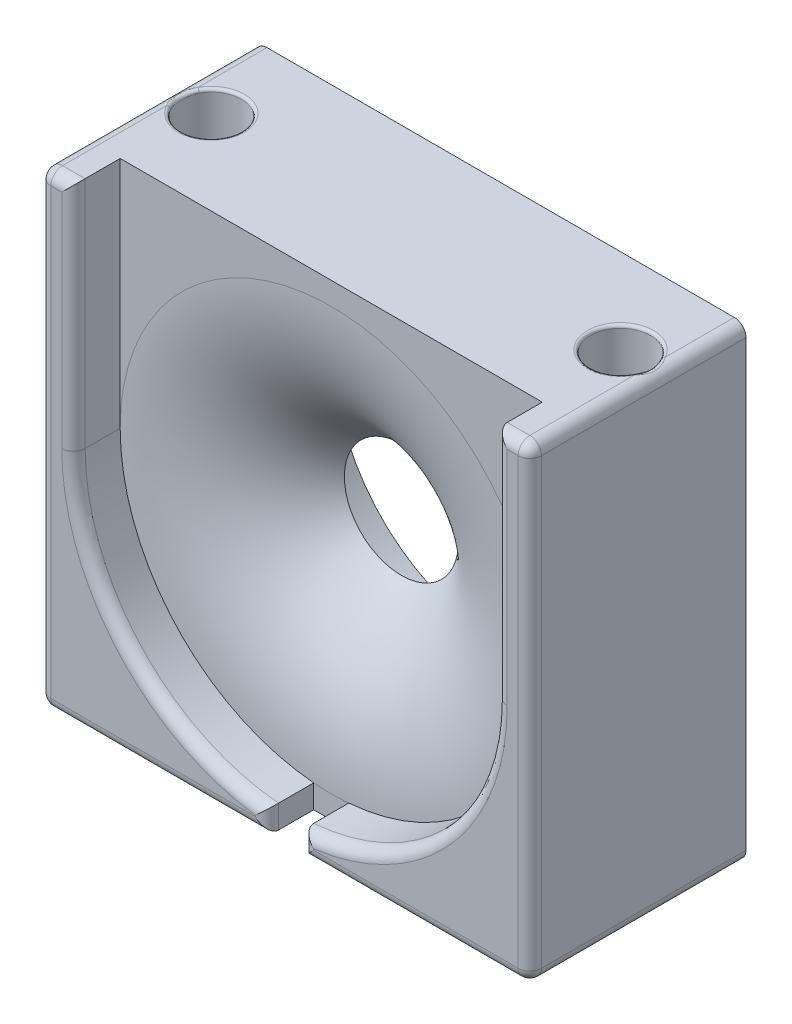
SolidWorks part; units mm, degrees
ref_plane "Front Plane" through (0, 0, 0) normal (1, 0, 0) x (0, 1, 0)
ref_plane "Top Plane" through (0, 0, 0) normal (0, 0, 1) x (0, 1, 0)
ref_plane "Right Plane" through (0, 0, 0) normal (0, 1, 0) x (-1, 0, 0)
sketch "Sketch1" plane through (0, 0, 0) normal (0, 0, 1) x (0, 1, 0)
  line L1 (-40, -42) -> (40, -42)
  line L2 (-40, -42) -> (-40, 42)
  line L3 (-40, 42) -> (40, 42)
  line L4 (40, -42) -> (40, 42)
  line L5 (-40, -42) -> (40, 42) construction
  line L6 (-40, 42) -> (40, -42) construction
  circle A0 centre (0, 0) radius 9.75
  point P0 (0, 0)
  dimension "D3" = 19.5
  dimension "D1" = 84
  dimension "D2" = 80
extrude "29 mm extrude" add sketch "Sketch1" along normal blind 29
sketch "Sketch2" plane through (0, 0, 0) normal (0, 0, -1) x (1, 0, 0)
  circle A0 centre (0, 0) radius 28.5
  dimension "D1" = 57
extrude "17 mm cut" cut sketch "Sketch2" against normal blind 17
fillet "25R funnel slope" radius 35 1 edges at (9.75, 0, 29)
sketch "Sketch3" plane through (0, 40, 0) normal (0, 1, 0) x (-1, 0, 0)
  line L0 (-42, 14.5) -> (42, 14.5) construction
  line L1 (-42, 29) -> (-42, 0) construction
  line L2 (42, 29) -> (42, 0) construction
  line L3 (0, 29) -> (0, 0) construction
  line L4 (-42, 29) -> (42, 29) construction
  line L5 (-42, 14.5) -> (-40.175, 14.5)
  circle A0 centre (-35.025, 14.5) radius 5.15
  circle A1 centre (35.025, 14.5) radius 5.15
  dimension "D1" = 10.3
extrude "36 mm cut screw head" cut sketch "Sketch3" against normal blind 36 contours A0 | A1 region at (35.025, 40, 14.5) region at (-35.025, 40, 14.5)
sketch "Sketch5" plane through (0, 40, 0) normal (0, 1, 0) x (-1, 0, 0)
  circle A0 centre (-35.025, 14.5) radius 3.9
  circle A1 centre (-35.025, 14.5) radius 5.15 construction
  dimension "D1" = 7.8
extrude "7.8mm bore" cut sketch "Sketch5" against normal through all
fillet "3R pig hole" radius 5 1 edges at (-28.5, 0, 17)
fillet "2R corners" radius 2 4 edges at (-42, 40, 14.5) (-42, -40, 14.5) (42, -40, 14.5) (42, 40, 14.5)
fillet "0.5R bolts" radius 0.5 4 edges at (-40.1603, 39.9936, 14.8885) (40.1603, 39.9936, 14.1115) (-29.875, 40, 14.5) (29.875, 40, 14.5)
mirror "Mirror1" about plane through (0, 0, 0) normal (1, 0, 0) of "7.8mm bore"
sketch "Sketch6" plane through (0, 0, 29) normal (0, 0, 1) x (1, 0, 0)
  line L0 (-42, 38) -> (-42, -38) construction
  line L1 (-42, 0) -> (42, 0)
  line L2 (-42, 38) -> (-42, -38)
  line L3 (-40, -40) -> (40, -40)
  line L4 (42, 38) -> (42, -38)
  line L5 (-42, 0) -> (42, -40) construction
  line L6 (-42, -40) -> (42, 0) construction
  line L7 (42, -38) -> (42, 38) construction
  line L8 (-40, -40) -> (40, -40) construction
  line L9 (-39, -3) -> (-39, -37)
  line L10 (-39, -37) -> (39, -37)
  line L11 (39, -3) -> (39, -37)
  line L12 (-39, -3) -> (39, -3)
  line L13 (-42, -3) -> (42, -3)
  line L14 (-42, 0) -> (-42, -40) construction
  line L15 (-42, -40) -> (42, -40) construction
  line L16 (42, 0) -> (42, -40) construction
  line L17 (0, -37) -> (0, -40) construction
  line L18 (-3, 31.0296) -> (3, 37) construction
  line L19 (-3, -40) -> (3, -40)
  line L20 (-3, -40) -> (-3, -37)
  line L21 (-3, -37) -> (3, -37)
  line L22 (3, -40) -> (3, -37)
  line L23 (-3, -40) -> (3, -37) construction
  line L24 (-3, -37) -> (3, -40) construction
  line L25 (-3, -37) -> (3, -37)
  line L26 (-3, -37) -> (-3, -31.0296)
  line L27 (-3, -31.0296) -> (3, -31.0296)
  line L28 (3, -37) -> (3, -31.0296)
  line L29 (-3, -37) -> (3, -31.0296) construction
  line L30 (-3, -31.0296) -> (3, -37) construction
  line L31 (-3, 37) -> (3, 31.0296) construction
  line L32 (-3, 37) -> (3, 40) construction
  line L33 (-3, 40) -> (3, 37) construction
  line L34 (0, 37) -> (0, 40) construction
  line L35 (-42, 40) -> (42, 0) construction
  line L36 (-42, 0) -> (42, 40) construction
  line L37 (3, 37) -> (3, 31.0296)
  line L38 (-3, 31.0296) -> (3, 31.0296)
  line L39 (-3, 37) -> (-3, 31.0296)
  line L40 (-3, 37) -> (3, 37)
  line L41 (3, 40) -> (3, 37)
  line L42 (-3, 37) -> (3, 37)
  line L43 (-3, 40) -> (-3, 37)
  line L44 (-3, 40) -> (3, 40)
  line L45 (-42, 3) -> (42, 3)
  line L46 (-39, 3) -> (39, 3)
  line L47 (39, 3) -> (39, 37)
  line L48 (-39, 37) -> (39, 37)
  line L49 (-39, 3) -> (-39, 37)
  line L50 (-40, 40) -> (40, 40)
  line L51 (-36.1318, 0) -> (-36.1318, 40)
  line L52 (36.1318, 0) -> (36.1318, 40)
  arc A0 (40, 40) -> (42, 38) centre (40, 38) cw
  arc A1 (-42, -38) -> (-40, -40) centre (-40, -38) ccw
  arc A2 (40, -40) -> (42, -38) centre (40, -38) ccw
  circle A3 centre (0, 0) radius 31.1743
  arc A4 (-42, 38) -> (-40, 40) centre (-40, 38) cw
  circle A5 centre (0, 0) radius 36.1318 construction
  point P4 (0, -20)
  point P19 (0, -38.5)
  point P36 (0, -34.0148)
  point P55 (0, 34.0148)
  point P56 (0, 38.5)
  point P61 (0, 20)
  circle M11 centre (0, 0) radius 36.1318
  line M12 (40, 40) -> (-40, 40)
  arc M13 (-40, 40) -> (-42, 38) centre (-40, 38) ccw
  line M14 (-42, 38) -> (-42, -38)
  arc M15 (-42, -38) -> (-40, -40) centre (-40, -38) ccw
  line M16 (-40, -40) -> (40, -40)
  arc M17 (40, -40) -> (42, -38) centre (40, -38) ccw
  line M18 (42, -38) -> (42, 38)
  arc M19 (42, 38) -> (40, 40) centre (40, 38) ccw
  dimension "D2" = 2
  dimension "D1" = 3
  dimension "D3" = 6
extrude "8 mm extrude" add sketch "Sketch6" along normal blind 8 contours L20 L10 L9 L13 L2 M16 M15 | L22 L13 L11 L10 M16 M17 M18 | L28 L10 L11 L12 M11 | L10 L26 L12 L9 M11 | L48 L51 L50 L45 L49 M13 M14 | L45 L51 L48 L49 | L52 L48 L47 L45 L4 M19 M12 | L52 L46 L47 L48 | L52 L1 L45 L46 M18 | L12 L13 L4 L1 M11 | L1 L51 L45 L2 | L13 L12 L1 M14 M11 region at (-39.0659, 1.5, 29) region at (-39.045, -1.5053, 29) region at (-40.2798, 22.6013, 29) region at (-40.5, -3.5376, 29) region at (-37.5659, 20, 29) region at (-29.7469, -26.7336, 29) region at (39.0659, 1.5, 29) region at (39.045, -1.5053, 29) region at (29.7469, -26.7336, 29) region at (37.5659, 20, 29) region at (21, -37.5376, 29) region at (40.2798, 22.6013, 29)
fillet "1R filet" radius 2 16 edges at (3, -38.0035, 37) (36.1318, 20, 37) (21.5, -40, 37) (41.4142, -39.4142, 37) (42, 0, 37) (41.4142, 39.4142, 37) (38.0659, 40, 37) (26.5886, -24.4654, 37) (-36.1318, 20, 37) (-38.0659, 40, 37) (-41.4142, 39.4142, 37) (-42, 0, 37) (-41.4142, -39.4142, 37) (-21.5, -40, 37) (-3, -38.0035, 37) (-26.5886, -24.4654, 37)
